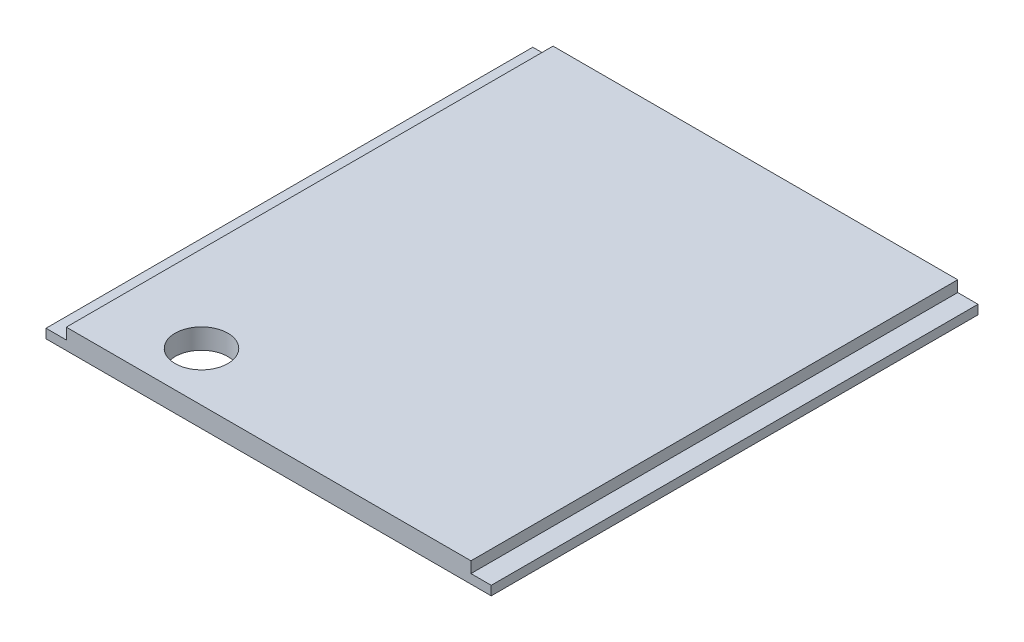
SolidWorks part; units mm, degrees
ref_plane "Front Plane" through (0, 0, 0) normal (0, 0, 1) x (1, 0, 0)
ref_plane "Top Plane" through (0, 0, 0) normal (0, 1, 0) x (1, 0, 0)
ref_plane "Right Plane" through (0, 0, 0) normal (1, 0, 0) x (0, 0, -1)
sketch "Sketch1" plane through (0, 0, 0) normal (0, 1, 0) x (1, 0, 0)
  line L1 (0, 0) -> (139.4003, 0)
  line L2 (0, 0) -> (0, 152.4)
  line L3 (0, 152.4) -> (139.4003, 152.4)
  line L4 (139.4003, 0) -> (139.4003, 152.4)
  dimension "D1" = 152.4
  dimension "D2" = 139.4003
extrude "Boss-Extrude1" add sketch "Sketch1" along normal blind 6.35
sketch "Sketch2" plane through (0, 6.35, 0) normal (0, 1, 0) x (1, 0, 0)
  line L0 (0, 0) -> (139.4003, 0) construction
  line L1 (0, 152.4) -> (6.35, 152.4)
  line L2 (0, 152.4) -> (0, 0)
  line L3 (0, 0) -> (6.35, 0)
  line L4 (6.35, 152.4) -> (6.35, 0)
  line L6 (139.4003, 152.4) -> (133.0503, 152.4)
  line L7 (139.4003, 152.4) -> (139.4003, 0)
  line L8 (139.4003, 0) -> (133.0503, 0)
  line L9 (133.0503, 152.4) -> (133.0503, 0)
  dimension "D1" = 6.35
  dimension "D2" = 6.35
extrude "Cut-Extrude1" cut sketch "Sketch2" against normal blind 3.4747
sketch "Sketch3" plane through (0, 6.35, 0) normal (0, 1, 0) x (1, 0, 0)
  line L0 (6.35, 0) -> (133.0503, 0) construction
  line L1 (6.35, 0) -> (6.35, 152.4) construction
  circle A0 centre (33.274, 15.4084) radius 8.255
  dimension "D1" = 16.51
  dimension "D2" = 15.4084
  dimension "D3" = 26.924
extrude "Cut-Extrude2" cut sketch "Sketch3" against normal through all
